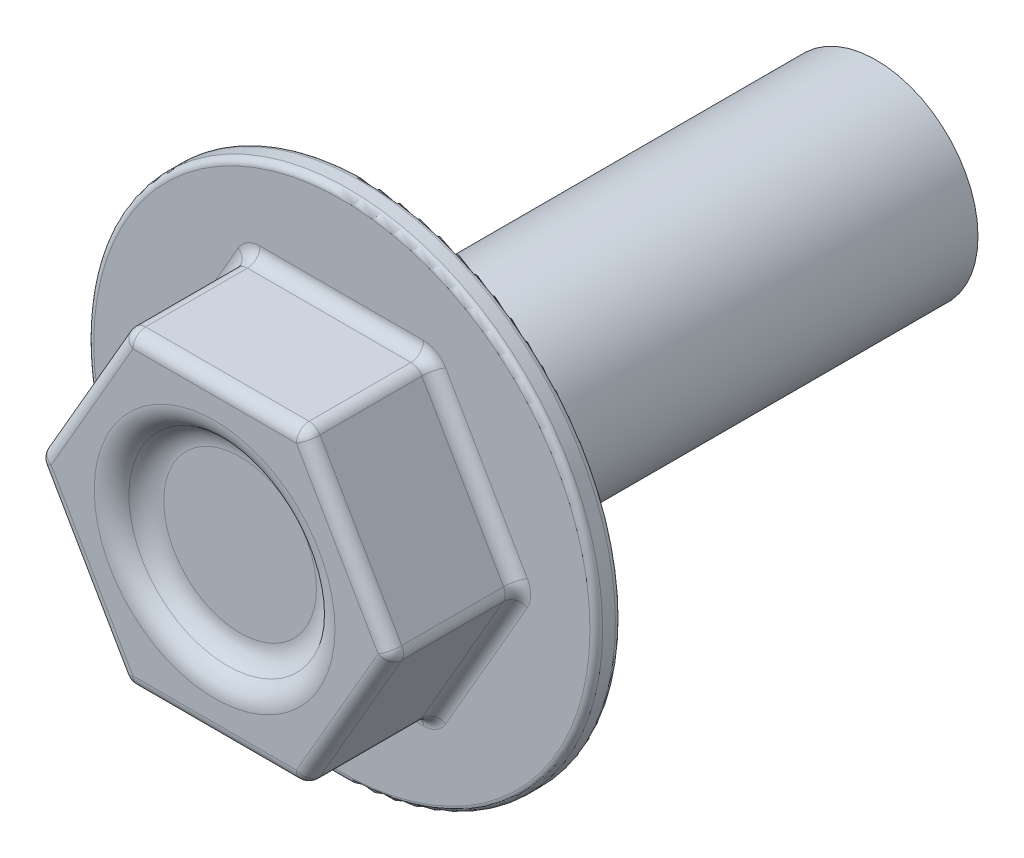
SolidWorks part; units mm, degrees
material "AISI 4140 Steel, quenched & tempered"
ref_plane "Front Plane" through (0, 0, 0) normal (1, 0, 0) x (0, 1, 0)
ref_plane "Top Plane" through (0, 0, 0) normal (0, 0, 1) x (0, 1, 0)
ref_plane "Right Plane" through (0, 0, 0) normal (0, 1, 0) x (-1, 0, 0)
sketch "Sketch1" plane through (0, 0, 0) normal (0, 0, 1) x (0, 1, 0)
  circle A0 centre (0, 0) radius 10
  circle A1 centre (0, 0) radius 20
  circle A2 centre (0, 0) radius 8
  dimension "D1" = 20
  dimension "D2" = 40
  dimension "D3" = 16
extrude "Boss-Extrude1" add sketch "Sketch1" against normal blind 40 contours A2
extrude "Boss-Extrude2" add sketch "Sketch1<3>" along normal blind 2 contours A1
sketch "Sketch1<3>" plane through (0, 0, 0) normal (0, 0, 1) x (0, 1, 0) same geometry as "Sketch1"
sketch "Sketch2" plane through (0, 0, 2) normal (0, 0, 1) x (1, 0, 0)
  line L1 (-14, 0) -> (-7, -12.1244)
  line L2 (-7, -12.1244) -> (7, -12.1244)
  line L3 (7, -12.1244) -> (14, 0)
  line L4 (14, 0) -> (7, 12.1244)
  line L5 (7, 12.1244) -> (-7, 12.1244)
  line L6 (-7, 12.1244) -> (-14, 0)
  circle A0 centre (0, 0) radius 12.1244 construction
  circle A1 centre (0, 0) radius 8
  dimension "D2" = 16
  dimension "D1" = 14
extrude "Boss-Extrude3" add sketch "Sketch2" along normal blind 10 contours L3 L4 L5 L6 L1 L2
extrude "Cut-Extrude1" cut sketch "Sketch2<3>" along normal up to surface (10 mm away) from offset 8 contours A1 up to face at (0, 0, 12)
sketch "Sketch2<3>" plane through (0, 0, 2) normal (0, 0, 1) x (1, 0, 0) same geometry as "Sketch2"
fillet "Fillet1" radius 0.5 2 edges at (20, 0, 0) (20, 0, 2)
fillet "Fillet2" radius 1 18 edges at (-7, -12.1244, 7) (-14, 0, 7) (-7, 12.1244, 7) (7, 12.1244, 7) (7, -12.1244, 7) (14, 0, 7) (-10.5, -6.0622, 12) (-10.5, 6.0622, 12) (0, 12.1244, 12) (10.5, -6.0622, 12) (0, -12.1244, 12) (10.5, 6.0622, 12) (10.5, -6.0622, 2) (0, 12.1244, 2) (-10.5, 6.0622, 2) (-10.5, -6.0622, 2) (0, -12.1244, 2) (10.5, 6.0622, 2)
fillet "Fillet3" radius 2 1 edges at (8, 0, 10)
fillet "Fillet4" radius 2 1 edges at (8, 0, 12)
